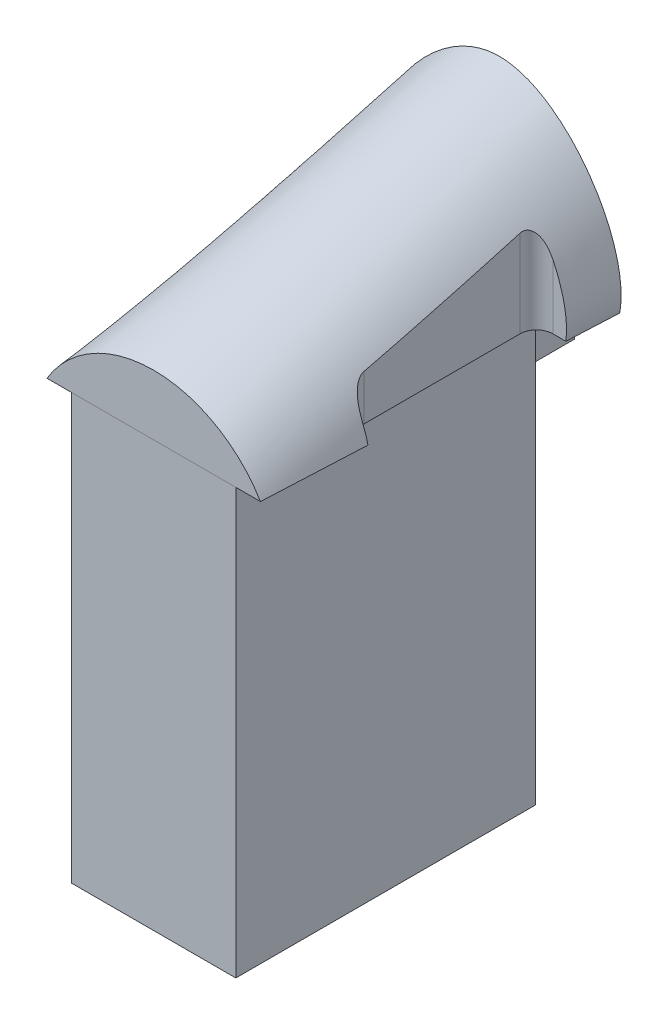
SolidWorks part; units mm, degrees
ref_plane "前视基准面" through (0, 0, 0) normal (0, 0, 1) x (1, 0, 0)
ref_plane "上视基准面" through (0, 0, 0) normal (0, 1, 0) x (1, 0, 0)
ref_plane "右视基准面" through (0, 0, 0) normal (1, 0, 0) x (0, 0, -1)
other "质心 (COM)"
sketch "草图1" plane through (0, 0, 0) normal (0, 1, 0) x (1, 0, 0)
  line L1 (-20, -36.5) -> (20, -36.5)
  line L2 (-20, -36.5) -> (-20, 36.5)
  line L3 (-20, 36.5) -> (20, 36.5)
  line L4 (20, -36.5) -> (20, 36.5)
  line L5 (-20, -36.5) -> (20, 36.5) construction
  line L6 (-20, 36.5) -> (20, -36.5) construction
  point P0 (0, 0)
  dimension "D1" = 40
  dimension "D2" = 73
extrude "凸台-拉伸1" add sketch "草图1" along normal mid plane 103.5
sketch "草图2" plane through (0, 0, -36.5) normal (0, 0, -1) x (-1, 0, 0)
  line L0 (-20, 51.75) -> (-20, -51.75) construction
  line L1 (-19, 51.75) -> (7.5, 51.75)
  line L2 (-19, 51.75) -> (-19, 40.75)
  line L3 (-19, 40.75) -> (7.5, 40.75)
  line L4 (7.5, 51.75) -> (7.5, 40.75)
  dimension "D1" = 11
  dimension "D2" = 26.5
  dimension "D3" = 1
extrude "凸台-拉伸2" add sketch "草图2" along normal blind 10.5
sketch "草图3" plane through (0, 0, -47) normal (0, 0, -1) x (-1, 0, 0)
  line L0 (-30, 51.75) -> (30, 51.75)
  line L2 (-20, -51.75) -> (20, -51.75) construction
  spline S0 degree 3 poles (-30, 51.75) (-32.9608, 67.553) (-0.1223, 116.2579) (33.0721, 64.9367) (30, 51.75) knots 0 0 0 0 0.500505 1 1 1 1
  point P4 (0, 51.75)
  point P12 (-16.8524, 83.8663)
  dimension "D1" = 60
  dimension "D2" = 143
sketch "草图4" plane through (0, 0, 36.5) normal (0, 0, 1) x (1, 0, 0)
  line L0 (-26, 51.75) -> (26, 51.75)
  line L1 (30, 51.75) -> (-30, 51.75) construction
  arc A0 (-26, 51.75) -> (26, 51.75) centre (0, 36.1214) cw
  point P4 (0, 51.75)
  dimension "D1" = 52
loft "放样1" add profiles "草图3", "草图4" connector at (30, 51.75, -47) connector at (26, 51.75, 36.5)
sketch "草图5" plane through (0, 51.75, 0) normal (0, -1, 0) x (1, 0, 0)
  line L0 (0, 13.4118) -> (0, -19.6269) construction
  line L1 (-27.3413, 11.5) -> (-26.243, 11.5)
  line L3 (-22.243, 7.5) -> (-22.243, -30.5)
  line L4 (-26.243, -34.5) -> (-29.4012, -34.5)
  line L5 (-29.4012, -34.5) -> (-36.9893, -34.5)
  line L6 (-26, 36.5) -> (26, 36.5) construction
  line L7 (36.9893, 12.3475) -> (27.3413, 11.5)
  line L8 (36.9893, -34.5) -> (36.9893, 12.3475)
  line L9 (29.4012, -34.5) -> (36.9893, -34.5)
  line L10 (26.243, -34.5) -> (29.4012, -34.5)
  line L12 (-36.9893, -34.5) -> (-36.9893, 12.3475)
  line L13 (-36.9893, 12.3475) -> (-27.3413, 11.5)
  line L14 (22.243, 7.5) -> (22.243, -30.5)
  line L15 (27.3413, 11.5) -> (26.243, 11.5)
  arc A0 (-22.243, -30.5) -> (-26.243, -34.5) centre (-26.243, -30.5) cw
  arc A1 (-22.243, 7.5) -> (-26.243, 11.5) centre (-26.243, 7.5) ccw
  arc A2 (22.243, 7.5) -> (26.243, 11.5) centre (26.243, 7.5) cw
  arc A3 (22.243, -30.5) -> (26.243, -34.5) centre (26.243, -30.5) ccw
  dimension "D3" = 4
  dimension "D1" = 25
  dimension "D2" = 71
extrude "切除-拉伸1" cut sketch "草图5" against normal through all
